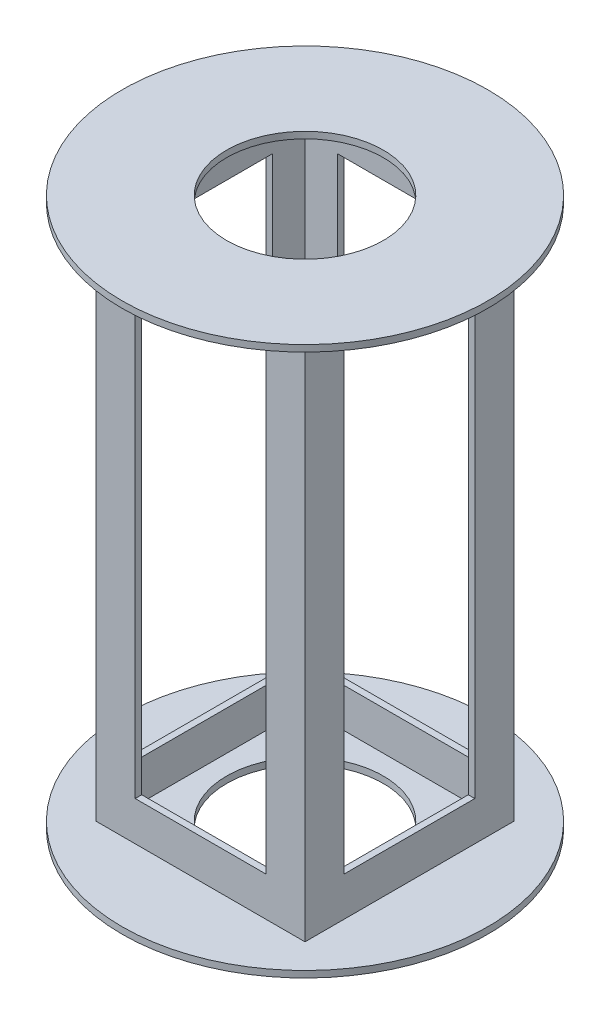
SolidWorks part; units mm, degrees
material "6061-T6 (SS)"
ref_plane "Front Plane" through (0, 0, 0) normal (0, 0, 1) x (1, 0, 0)
ref_plane "Top Plane" through (0, 0, 0) normal (0, 1, 0) x (1, 0, 0)
ref_plane "Right Plane" through (0, 0, 0) normal (1, 0, 0) x (0, 0, -1)
sketch "Sketch2" plane through (0, 0, 0) normal (0, 1, 0) x (1, 0, 0)
  line L0 (-47.625, 47.625) -> (47.625, 47.625)
  line L1 (-50.8, -50.8) -> (50.8, -50.8)
  line L2 (-50.8, -50.8) -> (-50.8, 50.8)
  line L3 (-50.8, 50.8) -> (50.8, 50.8)
  line L4 (50.8, -50.8) -> (50.8, 50.8)
  line L5 (-50.8, -50.8) -> (50.8, 50.8) construction
  line L6 (-50.8, 50.8) -> (50.8, -50.8) construction
  line L7 (47.625, -47.625) -> (47.625, 47.625)
  line L8 (-47.625, -47.625) -> (47.625, -47.625)
  line L9 (-47.625, -47.625) -> (-47.625, 47.625)
  circle A0 centre (0, 0) radius 88.9
  circle A1 centre (0, 0) radius 38.1
  dimension "D1" = 177.8
  dimension "D2" = 76.2
  dimension "D3" = 101.6
  dimension "D4" = 3.175
extrude "Boss-Extrude1" add sketch "Sketch2" along normal blind 3.175 contours A0 L4 L1 L2 L3 | L1 L4 L3 L2 A1 | L0 L7 L8 L9 | A1 region at (0, 0, -46.278) region at (-49.3632, 0, 0) region at (-86.3855, 0, 0)
extrude "Boss-Extrude2" add sketch "Sketch2<4>" along normal blind 266.7 contours L1 L4 L3 L2 L8 L9 L0 L7 region at (-49.3632, 0, 0)
sketch "Sketch2<4>" plane through (0, 0, 0) normal (0, 1, 0) x (1, 0, 0) same geometry as "Sketch2"
sketch "Sketch3" plane through (0, 266.7, 0) normal (0, 1, 0) x (1, 0, 0)
  circle A0 centre (0, 0) radius 38.1 construction
  circle A1 centre (0, 0) radius 88.9 construction
  circle A2 centre (0, 0) radius 38.1
  circle A3 centre (0, 0) radius 88.9
extrude "Boss-Extrude3" add sketch "Sketch3" against normal blind 3.175
sketch "Sketch4" plane through (0, 0, 0) normal (0, 0, 1) x (1, 0, 0)
  line L4 (50.8, 263.525) -> (-50.8, 263.525)
  line L5 (-50.8, 263.525) -> (-50.8, 3.175)
  line L6 (-50.8, 3.175) -> (50.8, 3.175)
  line L7 (50.8, 3.175) -> (50.8, 263.525)
  line L8 (50.8, 263.525) -> (-50.8, 263.525) construction
  line L9 (-50.8, 263.525) -> (-50.8, 3.175) construction
  line L10 (-50.8, 3.175) -> (50.8, 3.175) construction
  line L11 (50.8, 3.175) -> (50.8, 263.525) construction
  line L16 (31.75, 244.475) -> (-31.75, 244.475)
  line L17 (-31.75, 244.475) -> (-31.75, 22.225)
  line L18 (-31.75, 22.225) -> (31.75, 22.225)
  line L19 (31.75, 22.225) -> (31.75, 244.475)
  line L20 (31.75, 244.475) -> (-31.75, 244.475)
  line L21 (-31.75, 244.475) -> (-31.75, 22.225)
  line L22 (-31.75, 22.225) -> (31.75, 22.225)
  line L23 (31.75, 22.225) -> (31.75, 244.475)
  dimension "D1" = 0
  dimension "D2" = 19.05
extrude "Cut-Extrude1" cut sketch "Sketch4" against normal through all both and the other way through all
sketch "Sketch5" plane through (0, 0, 0) normal (1, 0, 0) x (0, 0, -1)
  line L4 (50.8, 263.525) -> (-50.8, 263.525)
  line L5 (-50.8, 263.525) -> (-50.8, 3.175)
  line L6 (-50.8, 3.175) -> (50.8, 3.175)
  line L7 (50.8, 3.175) -> (50.8, 263.525)
  line L8 (50.8, 263.525) -> (-50.8, 263.525) construction
  line L9 (-50.8, 263.525) -> (-50.8, 3.175) construction
  line L10 (-50.8, 3.175) -> (50.8, 3.175) construction
  line L11 (50.8, 3.175) -> (50.8, 263.525) construction
  line L16 (31.75, 244.475) -> (-31.75, 244.475)
  line L17 (-31.75, 244.475) -> (-31.75, 22.225)
  line L18 (-31.75, 22.225) -> (31.75, 22.225)
  line L19 (31.75, 22.225) -> (31.75, 244.475)
  line L20 (31.75, 244.475) -> (-31.75, 244.475)
  line L21 (-31.75, 244.475) -> (-31.75, 22.225)
  line L22 (-31.75, 22.225) -> (31.75, 22.225)
  line L23 (31.75, 22.225) -> (31.75, 244.475)
  dimension "D1" = 0
  dimension "D2" = 19.05
extrude "Cut-Extrude2" cut sketch "Sketch5" against normal through all both and the other way through all
